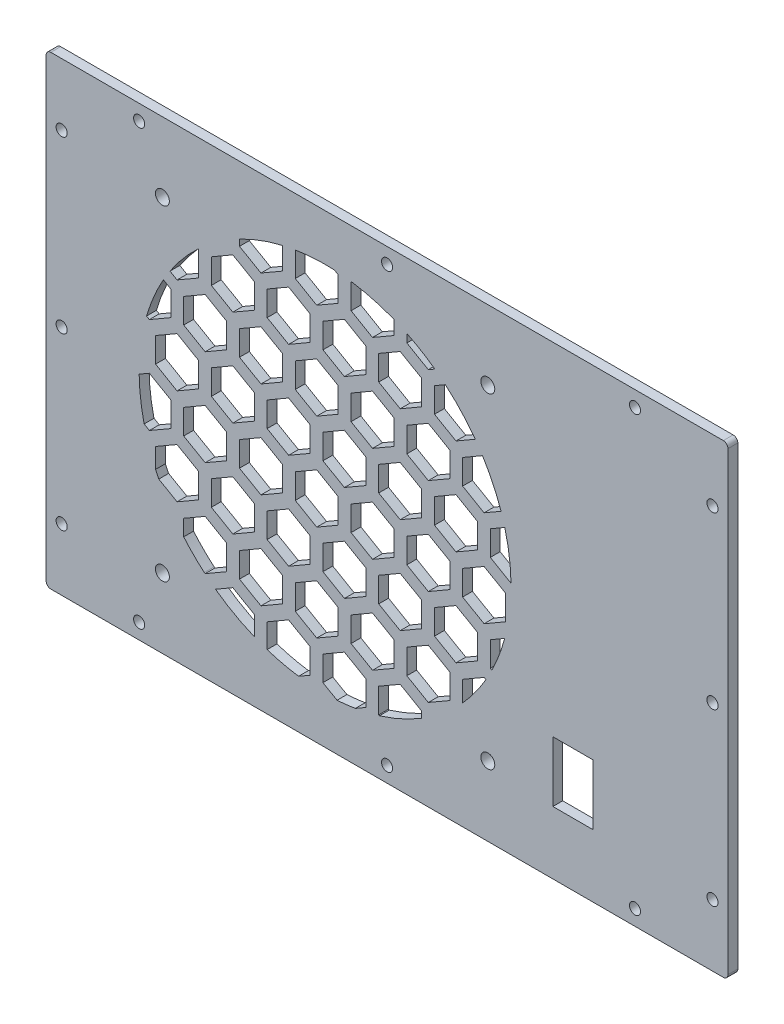
SolidWorks part; units mm, degrees
ref_plane "Front Plane" through (0, 0, 0) normal (0, 0, 1) x (1, 0, 0)
ref_plane "Top Plane" through (0, 0, 0) normal (0, 1, 0) x (1, 0, 0)
ref_plane "Right Plane" through (0, 0, 0) normal (1, 0, 0) x (0, 0, -1)
sketch "Sketch1" plane through (0, 0, 0) normal (0, 0, 1) x (1, 0, 0)
  line L0 (0, 0) -> (0, 75) construction
  line L1 (-110, -75) -> (110, -75)
  line L2 (-110, -75) -> (-110, 75)
  line L3 (-110, 75) -> (110, 75)
  line L4 (110, -75) -> (110, 75)
  line L5 (-110, -75) -> (110, 75) construction
  line L6 (-110, 75) -> (110, -75) construction
  line L15 (0, 0) -> (-110, 0) construction
  point P0 (0, 0)
  dimension "D1" = 220
  dimension "D2" = 150
extrude "Boss-Extrude1" add sketch "Sketch1" along normal blind 3.175 contours L3 L2 L1 L4 region at (0, 0, 0)
hole_wizard "M3 Clearance Hole1" positions "Sketch2" profile "Sketch3" hole size "M3" standard "ANSI Metric" end condition through all
sketch "Sketch2" plane through (0, 0, 3.175) normal (0, 0, 1) x (1, 0, 0)
  line L1 (-105, -70) -> (105, -70)
  line L2 (-105, -70) -> (-105, 70)
  line L3 (-105, 70) -> (105, 70)
  line L4 (105, -70) -> (105, 70)
  line L5 (-105, -70) -> (105, 70) construction
  line L6 (-105, 70) -> (105, -70) construction
  line L7 (-110, -75) -> (-110, 75) construction
  line L8 (-110, 75) -> (110, 75) construction
  point P2 (0, 0)
  point P113 (-80, 70)
  point P115 (80, 70)
  point P116 (0, 70)
  point P118 (-105, 55)
  point P120 (-105, 0)
  point P122 (-105, -55)
  point P124 (-80, -70)
  point P126 (0, -70)
  point P128 (80, -70)
  point P130 (105, -55)
  point P132 (105, 0)
  point P134 (105, 55)
  dimension "D1" = 5
  dimension "D2" = 5
  dimension "D3" = 80
  dimension "D4" = 80
  dimension "D5" = 55
  dimension "D6" = 55
sketch "Sketch3" plane through (0, 0, 3.175) normal (1, 0, 0) x (0, -1, 0)
  line L0 (0, 0) -> (0, 3.175)
  line L1 (0, 3.175) -> (1.8, 3.175)
  line L2 (1.8, 3.175) -> (1.8, 0)
  line L5 (1.8, 0) -> (0, 0)
  line L11 (0, -6.35) -> (0, 107.95) construction
  dimension "Thru Hole Dia." = 3.6
  dimension "Thru Hole Depth" = 3.175
sketch "Sketch4" plane through (0, 0, 3.175) normal (0, 0, 1) x (1, 0, 0)
  line L1 (-5, -5) -> (5, -5)
  line L2 (-5, -5) -> (-5, 5)
  line L3 (-5, 5) -> (5, 5)
  line L4 (5, -5) -> (5, 5)
  line L5 (-5, -5) -> (5, 5) construction
  line L6 (-5, 5) -> (5, -5) construction
  point P0 (0, 0)
  dimension "D1" = 10
  dimension "D2" = 10
extrude "Boss-Extrude2" add sketch "Sketch4" against normal through all
fillet "Fillet2" radius 1.5 4 edges at (-110, -75, 1.5875) (110, -75, 1.5875) (110, 75, 1.5875) (-110, 75, 1.5875)
sketch "Sketch6" plane through (0, 0, 3.175) normal (0, 0, 1) x (1, 0, 0)
  line L0 (-108.5, -75) -> (108.5, -75) construction
  line L1 (-80, -60) -> (40, -60)
  line L2 (-80, -60) -> (-80, 60)
  line L3 (-80, 60) -> (40, 60)
  line L4 (40, -60) -> (40, 60)
  line L5 (-80, -60) -> (40, 60) construction
  line L6 (-80, 60) -> (40, -60) construction
  line L13 (-110, -73.5) -> (-110, 73.5) construction
  line L17 (-72.5, -52.5) -> (32.5, -52.5)
  line L18 (-72.5, -52.5) -> (-72.5, 52.5)
  line L19 (-72.5, 52.5) -> (32.5, 52.5)
  line L20 (32.5, -52.5) -> (32.5, 52.5)
  line L21 (-72.5, -52.5) -> (32.5, 52.5) construction
  line L22 (-72.5, 52.5) -> (32.5, -52.5) construction
  circle A0 centre (-20, 0) radius 60
  point P0 (-20, 0)
  point P5 (-20, 0)
  point P6 (-20, 0)
  dimension "D7" = 120
  dimension "D1" = 120
  dimension "D2" = 120
  dimension "D3" = 15
  dimension "D4" = 30
  dimension "D5" = 105
  dimension "D6" = 105
hole_wizard "M4 Clearance Hole1" positions "Sketch7" profile "Sketch9" hole size "M4" standard "ANSI Metric" end condition through all
sketch "Sketch7" plane through (0, 0, 3.175) normal (0, 0, 1) x (1, 0, 0)
  point P0 (-72.5, 52.5)
  point P3 (32.5, 52.5)
  point P6 (32.5, -52.5)
  point P9 (-72.5, -52.5)
sketch "Sketch9" plane through (-72.5, 52.5, 3.175) normal (1, 0, 0) x (0, -1, 0)
  line L0 (0, 0) -> (0, 3.175)
  line L1 (0, 3.175) -> (2.25, 3.175)
  line L2 (2.25, 3.175) -> (2.25, 0)
  line L5 (2.25, 0) -> (0, 0)
  line L11 (0, -6.35) -> (0, 107.95) construction
  dimension "Thru Hole Dia." = 4.5
  dimension "Thru Hole Depth" = 3.175
extrude "Cut-Extrude1" cut sketch "Sketch6" against normal blind 10 contours L20 A0 L19 L18 L17 | L18 A0 | L19 A0 | A0 L20 | L17 A0 region at (-20, -55.5167, 3.175) region at (-75.5167, 0, 3.175) region at (-20, 0, 3.175) region at (35.5167, 0, 3.175) region at (-20, 55.5167, 3.175)
sketch "Sketch11" plane through (0, 0, 3.175) normal (0, 0, 1) x (1, 0, 0)
  line L0 (-58.6995, -29.7786) -> (-65.6277, -33.7786)
  line L1 (-76.6995, -29.7786) -> (-83.6277, -33.7786)
  line L2 (-83.6277, -33.7786) -> (-83.6277, -41.7786)
  line L3 (-83.6277, -41.7786) -> (-76.6995, -45.7786)
  line L4 (-76.6995, -45.7786) -> (-69.7713, -41.7786)
  line L5 (-69.7713, -41.7786) -> (-69.7713, -33.7786)
  line L6 (-69.7713, -33.7786) -> (-76.6995, -29.7786)
  line L13 (-67.7713, -45.2427) -> (-74.6995, -49.2427)
  line L14 (-74.6995, -49.2427) -> (-74.6995, -57.2427)
  line L15 (-74.6995, -57.2427) -> (-67.7713, -61.2427)
  line L16 (-67.7713, -61.2427) -> (-60.8431, -57.2427)
  line L17 (-60.8431, -57.2427) -> (-60.8431, -49.2427)
  line L18 (-60.8431, -49.2427) -> (-67.7713, -45.2427)
  line L19 (-65.6277, -33.7786) -> (-65.6277, -41.7786)
  line L20 (-65.6277, -41.7786) -> (-58.6995, -45.7786)
  line L21 (-58.6995, -45.7786) -> (-51.7713, -41.7786)
  line L22 (-51.7713, -41.7786) -> (-51.7713, -33.7786)
  line L23 (-51.7713, -33.7786) -> (-58.6995, -29.7786)
  line L24 (-49.7713, -45.2427) -> (-56.6995, -49.2427)
  line L25 (-56.6995, -49.2427) -> (-56.6995, -57.2427)
  line L26 (-56.6995, -57.2427) -> (-49.7713, -61.2427)
  line L27 (-49.7713, -61.2427) -> (-42.8431, -57.2427)
  line L28 (-42.8431, -57.2427) -> (-42.8431, -49.2427)
  line L29 (-42.8431, -49.2427) -> (-49.7713, -45.2427)
  line L30 (-40.6995, -29.7786) -> (-47.6277, -33.7786)
  line L31 (-47.6277, -33.7786) -> (-47.6277, -41.7786)
  line L32 (-47.6277, -41.7786) -> (-40.6995, -45.7786)
  line L33 (-40.6995, -45.7786) -> (-33.7713, -41.7786)
  line L34 (-33.7713, -41.7786) -> (-33.7713, -33.7786)
  line L35 (-33.7713, -33.7786) -> (-40.6995, -29.7786)
  line L36 (-31.7713, -45.2427) -> (-38.6995, -49.2427)
  line L37 (-38.6995, -49.2427) -> (-38.6995, -57.2427)
  line L38 (-38.6995, -57.2427) -> (-31.7713, -61.2427)
  line L39 (-31.7713, -61.2427) -> (-24.8431, -57.2427)
  line L40 (-24.8431, -57.2427) -> (-24.8431, -49.2427)
  line L41 (-24.8431, -49.2427) -> (-31.7713, -45.2427)
  line L42 (-22.6995, -29.7786) -> (-29.6277, -33.7786)
  line L43 (-29.6277, -33.7786) -> (-29.6277, -41.7786)
  line L44 (-29.6277, -41.7786) -> (-22.6995, -45.7786)
  line L45 (-22.6995, -45.7786) -> (-15.7713, -41.7786)
  line L46 (-15.7713, -41.7786) -> (-15.7713, -33.7786)
  line L47 (-15.7713, -33.7786) -> (-22.6995, -29.7786)
  line L48 (-13.7713, -45.2427) -> (-20.6995, -49.2427)
  line L49 (-20.6995, -49.2427) -> (-20.6995, -57.2427)
  line L50 (-20.6995, -57.2427) -> (-13.7713, -61.2427)
  line L51 (-13.7713, -61.2427) -> (-6.8431, -57.2427)
  line L52 (-6.8431, -57.2427) -> (-6.8431, -49.2427)
  line L53 (-6.8431, -49.2427) -> (-13.7713, -45.2427)
  line L54 (-4.6995, -29.7786) -> (-11.6277, -33.7786)
  line L55 (-11.6277, -33.7786) -> (-11.6277, -41.7786)
  line L56 (-11.6277, -41.7786) -> (-4.6995, -45.7786)
  line L57 (-4.6995, -45.7786) -> (2.2287, -41.7786)
  line L58 (2.2287, -41.7786) -> (2.2287, -33.7786)
  line L59 (2.2287, -33.7786) -> (-4.6995, -29.7786)
  line L60 (4.2287, -45.2427) -> (-2.6995, -49.2427)
  line L61 (-2.6995, -49.2427) -> (-2.6995, -57.2427)
  line L62 (-2.6995, -57.2427) -> (4.2287, -61.2427)
  line L63 (4.2287, -61.2427) -> (11.1569, -57.2427)
  line L64 (11.1569, -57.2427) -> (11.1569, -49.2427)
  line L65 (11.1569, -49.2427) -> (4.2287, -45.2427)
  line L66 (13.3005, -29.7786) -> (6.3723, -33.7786)
  line L67 (6.3723, -33.7786) -> (6.3723, -41.7786)
  line L68 (6.3723, -41.7786) -> (13.3005, -45.7786)
  line L69 (13.3005, -45.7786) -> (20.2287, -41.7786)
  line L70 (20.2287, -41.7786) -> (20.2287, -33.7786)
  line L71 (20.2287, -33.7786) -> (13.3005, -29.7786)
  line L72 (22.2287, -45.2427) -> (15.3005, -49.2427)
  line L73 (15.3005, -49.2427) -> (15.3005, -57.2427)
  line L74 (15.3005, -57.2427) -> (22.2287, -61.2427)
  line L75 (22.2287, -61.2427) -> (29.1569, -57.2427)
  line L76 (29.1569, -57.2427) -> (29.1569, -49.2427)
  line L77 (29.1569, -49.2427) -> (22.2287, -45.2427)
  line L78 (31.3005, -29.7786) -> (24.3723, -33.7786)
  line L79 (24.3723, -33.7786) -> (24.3723, -41.7786)
  line L80 (24.3723, -41.7786) -> (31.3005, -45.7786)
  line L81 (31.3005, -45.7786) -> (38.2287, -41.7786)
  line L82 (38.2287, -41.7786) -> (38.2287, -33.7786)
  line L83 (38.2287, -33.7786) -> (31.3005, -29.7786)
  line L84 (40.2287, -45.2427) -> (33.3005, -49.2427)
  line L85 (33.3005, -49.2427) -> (33.3005, -57.2427)
  line L86 (33.3005, -57.2427) -> (40.2287, -61.2427)
  line L87 (40.2287, -61.2427) -> (47.1569, -57.2427)
  line L88 (47.1569, -57.2427) -> (47.1569, -49.2427)
  line L89 (47.1569, -49.2427) -> (40.2287, -45.2427)
  line L90 (-58.6995, 1.2214) -> (-65.6277, -2.7786)
  line L91 (-65.6277, -2.7786) -> (-65.6277, -10.7786)
  line L92 (-65.6277, -10.7786) -> (-58.6995, -14.7786)
  line L93 (-58.6995, -14.7786) -> (-51.7713, -10.7786)
  line L94 (-51.7713, -10.7786) -> (-51.7713, -2.7786)
  line L95 (-51.7713, -2.7786) -> (-58.6995, 1.2214)
  line L96 (-49.7713, -14.2427) -> (-56.6995, -18.2427)
  line L97 (-56.6995, -18.2427) -> (-56.6995, -26.2427)
  line L98 (-56.6995, -26.2427) -> (-49.7713, -30.2427)
  line L99 (-49.7713, -30.2427) -> (-42.8431, -26.2427)
  line L100 (-42.8431, -26.2427) -> (-42.8431, -18.2427)
  line L101 (-42.8431, -18.2427) -> (-49.7713, -14.2427)
  line L102 (-40.6995, 1.2214) -> (-47.6277, -2.7786)
  line L103 (-47.6277, -2.7786) -> (-47.6277, -10.7786)
  line L104 (-47.6277, -10.7786) -> (-40.6995, -14.7786)
  line L105 (-40.6995, -14.7786) -> (-33.7713, -10.7786)
  line L106 (-33.7713, -10.7786) -> (-33.7713, -2.7786)
  line L107 (-33.7713, -2.7786) -> (-40.6995, 1.2214)
  line L108 (-31.7713, -14.2427) -> (-38.6995, -18.2427)
  line L109 (-38.6995, -18.2427) -> (-38.6995, -26.2427)
  line L110 (-38.6995, -26.2427) -> (-31.7713, -30.2427)
  line L111 (-31.7713, -30.2427) -> (-24.8431, -26.2427)
  line L112 (-24.8431, -26.2427) -> (-24.8431, -18.2427)
  line L113 (-24.8431, -18.2427) -> (-31.7713, -14.2427)
  line L114 (-22.6995, 1.2214) -> (-29.6277, -2.7786)
  line L115 (-29.6277, -2.7786) -> (-29.6277, -10.7786)
  line L116 (-29.6277, -10.7786) -> (-22.6995, -14.7786)
  line L117 (-22.6995, -14.7786) -> (-15.7713, -10.7786)
  line L118 (-15.7713, -10.7786) -> (-15.7713, -2.7786)
  line L119 (-15.7713, -2.7786) -> (-22.6995, 1.2214)
  line L120 (-13.7713, -14.2427) -> (-20.6995, -18.2427)
  line L121 (-20.6995, -18.2427) -> (-20.6995, -26.2427)
  line L122 (-20.6995, -26.2427) -> (-13.7713, -30.2427)
  line L123 (-13.7713, -30.2427) -> (-6.8431, -26.2427)
  line L124 (-6.8431, -26.2427) -> (-6.8431, -18.2427)
  line L125 (-6.8431, -18.2427) -> (-13.7713, -14.2427)
  line L126 (-4.6995, 1.2214) -> (-11.6277, -2.7786)
  line L127 (-11.6277, -2.7786) -> (-11.6277, -10.7786)
  line L128 (-11.6277, -10.7786) -> (-4.6995, -14.7786)
  line L129 (-4.6995, -14.7786) -> (2.2287, -10.7786)
  line L130 (2.2287, -10.7786) -> (2.2287, -2.7786)
  line L131 (2.2287, -2.7786) -> (-4.6995, 1.2214)
  line L132 (4.2287, -14.2427) -> (-2.6995, -18.2427)
  line L133 (-2.6995, -18.2427) -> (-2.6995, -26.2427)
  line L134 (-2.6995, -26.2427) -> (4.2287, -30.2427)
  line L135 (4.2287, -30.2427) -> (11.1569, -26.2427)
  line L136 (11.1569, -26.2427) -> (11.1569, -18.2427)
  line L137 (11.1569, -18.2427) -> (4.2287, -14.2427)
  line L138 (13.3005, 1.2214) -> (6.3723, -2.7786)
  line L139 (6.3723, -2.7786) -> (6.3723, -10.7786)
  line L140 (6.3723, -10.7786) -> (13.3005, -14.7786)
  line L141 (13.3005, -14.7786) -> (20.2287, -10.7786)
  line L142 (20.2287, -10.7786) -> (20.2287, -2.7786)
  line L143 (20.2287, -2.7786) -> (13.3005, 1.2214)
  line L144 (22.2287, -14.2427) -> (15.3005, -18.2427)
  line L145 (15.3005, -18.2427) -> (15.3005, -26.2427)
  line L146 (15.3005, -26.2427) -> (22.2287, -30.2427)
  line L147 (22.2287, -30.2427) -> (29.1569, -26.2427)
  line L148 (29.1569, -26.2427) -> (29.1569, -18.2427)
  line L149 (29.1569, -18.2427) -> (22.2287, -14.2427)
  line L150 (31.3005, 1.2214) -> (24.3723, -2.7786)
  line L151 (24.3723, -2.7786) -> (24.3723, -10.7786)
  line L152 (24.3723, -10.7786) -> (31.3005, -14.7786)
  line L153 (31.3005, -14.7786) -> (38.2287, -10.7786)
  line L154 (38.2287, -10.7786) -> (38.2287, -2.7786)
  line L155 (38.2287, -2.7786) -> (31.3005, 1.2214)
  line L156 (40.2287, -14.2427) -> (33.3005, -18.2427)
  line L157 (33.3005, -18.2427) -> (33.3005, -26.2427)
  line L158 (33.3005, -26.2427) -> (40.2287, -30.2427)
  line L159 (40.2287, -30.2427) -> (47.1569, -26.2427)
  line L160 (47.1569, -26.2427) -> (47.1569, -18.2427)
  line L161 (47.1569, -18.2427) -> (40.2287, -14.2427)
  line L162 (-58.6995, 32.2214) -> (-65.6277, 28.2214)
  line L163 (-65.6277, 28.2214) -> (-65.6277, 20.2214)
  line L164 (-65.6277, 20.2214) -> (-58.6995, 16.2214)
  line L165 (-58.6995, 16.2214) -> (-51.7713, 20.2214)
  line L166 (-51.7713, 20.2214) -> (-51.7713, 28.2214)
  line L167 (-51.7713, 28.2214) -> (-58.6995, 32.2214)
  line L168 (-49.7713, 16.7573) -> (-56.6995, 12.7573)
  line L169 (-56.6995, 12.7573) -> (-56.6995, 4.7573)
  line L170 (-56.6995, 4.7573) -> (-49.7713, 0.7573)
  line L171 (-49.7713, 0.7573) -> (-42.8431, 4.7573)
  line L172 (-42.8431, 4.7573) -> (-42.8431, 12.7573)
  line L173 (-42.8431, 12.7573) -> (-49.7713, 16.7573)
  line L174 (-40.6995, 32.2214) -> (-47.6277, 28.2214)
  line L175 (-47.6277, 28.2214) -> (-47.6277, 20.2214)
  line L176 (-47.6277, 20.2214) -> (-40.6995, 16.2214)
  line L177 (-40.6995, 16.2214) -> (-33.7713, 20.2214)
  line L178 (-33.7713, 20.2214) -> (-33.7713, 28.2214)
  line L179 (-33.7713, 28.2214) -> (-40.6995, 32.2214)
  line L180 (-31.7713, 16.7573) -> (-38.6995, 12.7573)
  line L181 (-38.6995, 12.7573) -> (-38.6995, 4.7573)
  line L182 (-38.6995, 4.7573) -> (-31.7713, 0.7573)
  line L183 (-31.7713, 0.7573) -> (-24.8431, 4.7573)
  line L184 (-24.8431, 4.7573) -> (-24.8431, 12.7573)
  line L185 (-24.8431, 12.7573) -> (-31.7713, 16.7573)
  line L186 (-22.6995, 32.2214) -> (-29.6277, 28.2214)
  line L187 (-29.6277, 28.2214) -> (-29.6277, 20.2214)
  line L188 (-29.6277, 20.2214) -> (-22.6995, 16.2214)
  line L189 (-22.6995, 16.2214) -> (-15.7713, 20.2214)
  line L190 (-15.7713, 20.2214) -> (-15.7713, 28.2214)
  line L191 (-15.7713, 28.2214) -> (-22.6995, 32.2214)
  line L192 (-13.7713, 16.7573) -> (-20.6995, 12.7573)
  line L193 (-20.6995, 12.7573) -> (-20.6995, 4.7573)
  line L194 (-20.6995, 4.7573) -> (-13.7713, 0.7573)
  line L195 (-13.7713, 0.7573) -> (-6.8431, 4.7573)
  line L196 (-6.8431, 4.7573) -> (-6.8431, 12.7573)
  line L197 (-6.8431, 12.7573) -> (-13.7713, 16.7573)
  line L198 (-4.6995, 32.2214) -> (-11.6277, 28.2214)
  line L199 (-11.6277, 28.2214) -> (-11.6277, 20.2214)
  line L200 (-11.6277, 20.2214) -> (-4.6995, 16.2214)
  line L201 (-4.6995, 16.2214) -> (2.2287, 20.2214)
  line L202 (2.2287, 20.2214) -> (2.2287, 28.2214)
  line L203 (2.2287, 28.2214) -> (-4.6995, 32.2214)
  line L204 (4.2287, 16.7573) -> (-2.6995, 12.7573)
  line L205 (-2.6995, 12.7573) -> (-2.6995, 4.7573)
  line L206 (-2.6995, 4.7573) -> (4.2287, 0.7573)
  line L207 (4.2287, 0.7573) -> (11.1569, 4.7573)
  line L208 (11.1569, 4.7573) -> (11.1569, 12.7573)
  line L209 (11.1569, 12.7573) -> (4.2287, 16.7573)
  line L210 (13.3005, 32.2214) -> (6.3723, 28.2214)
  line L211 (6.3723, 28.2214) -> (6.3723, 20.2214)
  line L212 (6.3723, 20.2214) -> (13.3005, 16.2214)
  line L213 (13.3005, 16.2214) -> (20.2287, 20.2214)
  line L214 (20.2287, 20.2214) -> (20.2287, 28.2214)
  line L215 (20.2287, 28.2214) -> (13.3005, 32.2214)
  line L216 (22.2287, 16.7573) -> (15.3005, 12.7573)
  line L217 (15.3005, 12.7573) -> (15.3005, 4.7573)
  line L218 (15.3005, 4.7573) -> (22.2287, 0.7573)
  line L219 (22.2287, 0.7573) -> (29.1569, 4.7573)
  line L220 (29.1569, 4.7573) -> (29.1569, 12.7573)
  line L221 (29.1569, 12.7573) -> (22.2287, 16.7573)
  line L222 (31.3005, 32.2214) -> (24.3723, 28.2214)
  line L223 (24.3723, 28.2214) -> (24.3723, 20.2214)
  line L224 (24.3723, 20.2214) -> (31.3005, 16.2214)
  line L225 (31.3005, 16.2214) -> (38.2287, 20.2214)
  line L226 (38.2287, 20.2214) -> (38.2287, 28.2214)
  line L227 (38.2287, 28.2214) -> (31.3005, 32.2214)
  line L228 (40.2287, 16.7573) -> (33.3005, 12.7573)
  line L229 (33.3005, 12.7573) -> (33.3005, 4.7573)
  line L230 (33.3005, 4.7573) -> (40.2287, 0.7573)
  line L231 (40.2287, 0.7573) -> (47.1569, 4.7573)
  line L232 (47.1569, 4.7573) -> (47.1569, 12.7573)
  line L233 (47.1569, 12.7573) -> (40.2287, 16.7573)
  line L234 (-58.6995, 63.2214) -> (-65.6277, 59.2214)
  line L235 (-65.6277, 59.2214) -> (-65.6277, 51.2214)
  line L236 (-65.6277, 51.2214) -> (-58.6995, 47.2214)
  line L237 (-58.6995, 47.2214) -> (-51.7713, 51.2214)
  line L238 (-51.7713, 51.2214) -> (-51.7713, 59.2214)
  line L239 (-51.7713, 59.2214) -> (-58.6995, 63.2214)
  line L240 (-49.7713, 47.7573) -> (-56.6995, 43.7573)
  line L241 (-56.6995, 43.7573) -> (-56.6995, 35.7573)
  line L242 (-56.6995, 35.7573) -> (-49.7713, 31.7573)
  line L243 (-49.7713, 31.7573) -> (-42.8431, 35.7573)
  line L244 (-42.8431, 35.7573) -> (-42.8431, 43.7573)
  line L245 (-42.8431, 43.7573) -> (-49.7713, 47.7573)
  line L246 (-40.6995, 63.2214) -> (-47.6277, 59.2214)
  line L247 (-47.6277, 59.2214) -> (-47.6277, 51.2214)
  line L248 (-47.6277, 51.2214) -> (-40.6995, 47.2214)
  line L249 (-40.6995, 47.2214) -> (-33.7713, 51.2214)
  line L250 (-33.7713, 51.2214) -> (-33.7713, 59.2214)
  line L251 (-33.7713, 59.2214) -> (-40.6995, 63.2214)
  line L252 (-31.7713, 47.7573) -> (-38.6995, 43.7573)
  line L253 (-38.6995, 43.7573) -> (-38.6995, 35.7573)
  line L254 (-38.6995, 35.7573) -> (-31.7713, 31.7573)
  line L255 (-31.7713, 31.7573) -> (-24.8431, 35.7573)
  line L256 (-24.8431, 35.7573) -> (-24.8431, 43.7573)
  line L257 (-24.8431, 43.7573) -> (-31.7713, 47.7573)
  line L258 (-22.6995, 63.2214) -> (-29.6277, 59.2214)
  line L259 (-29.6277, 59.2214) -> (-29.6277, 51.2214)
  line L260 (-29.6277, 51.2214) -> (-22.6995, 47.2214)
  line L261 (-22.6995, 47.2214) -> (-15.7713, 51.2214)
  line L262 (-15.7713, 51.2214) -> (-15.7713, 59.2214)
  line L263 (-15.7713, 59.2214) -> (-22.6995, 63.2214)
  line L264 (-13.7713, 47.7573) -> (-20.6995, 43.7573)
  line L265 (-20.6995, 43.7573) -> (-20.6995, 35.7573)
  line L266 (-20.6995, 35.7573) -> (-13.7713, 31.7573)
  line L267 (-13.7713, 31.7573) -> (-6.8431, 35.7573)
  line L268 (-6.8431, 35.7573) -> (-6.8431, 43.7573)
  line L269 (-6.8431, 43.7573) -> (-13.7713, 47.7573)
  line L270 (-4.6995, 63.2214) -> (-11.6277, 59.2214)
  line L271 (-11.6277, 59.2214) -> (-11.6277, 51.2214)
  line L272 (-11.6277, 51.2214) -> (-4.6995, 47.2214)
  line L273 (-4.6995, 47.2214) -> (2.2287, 51.2214)
  line L274 (2.2287, 51.2214) -> (2.2287, 59.2214)
  line L275 (2.2287, 59.2214) -> (-4.6995, 63.2214)
  line L276 (4.2287, 47.7573) -> (-2.6995, 43.7573)
  line L277 (-2.6995, 43.7573) -> (-2.6995, 35.7573)
  line L278 (-2.6995, 35.7573) -> (4.2287, 31.7573)
  line L279 (4.2287, 31.7573) -> (11.1569, 35.7573)
  line L280 (11.1569, 35.7573) -> (11.1569, 43.7573)
  line L281 (11.1569, 43.7573) -> (4.2287, 47.7573)
  line L282 (13.3005, 63.2214) -> (6.3723, 59.2214)
  line L283 (6.3723, 59.2214) -> (6.3723, 51.2214)
  line L284 (6.3723, 51.2214) -> (13.3005, 47.2214)
  line L285 (13.3005, 47.2214) -> (20.2287, 51.2214)
  line L286 (20.2287, 51.2214) -> (20.2287, 59.2214)
  line L287 (20.2287, 59.2214) -> (13.3005, 63.2214)
  line L288 (22.2287, 47.7573) -> (15.3005, 43.7573)
  line L289 (15.3005, 43.7573) -> (15.3005, 35.7573)
  line L290 (15.3005, 35.7573) -> (22.2287, 31.7573)
  line L291 (22.2287, 31.7573) -> (29.1569, 35.7573)
  line L292 (29.1569, 35.7573) -> (29.1569, 43.7573)
  line L293 (29.1569, 43.7573) -> (22.2287, 47.7573)
  line L294 (31.3005, 63.2214) -> (24.3723, 59.2214)
  line L295 (24.3723, 59.2214) -> (24.3723, 51.2214)
  line L296 (24.3723, 51.2214) -> (31.3005, 47.2214)
  line L297 (31.3005, 47.2214) -> (38.2287, 51.2214)
  line L298 (38.2287, 51.2214) -> (38.2287, 59.2214)
  line L299 (38.2287, 59.2214) -> (31.3005, 63.2214)
  line L300 (40.2287, 47.7573) -> (33.3005, 43.7573)
  line L301 (33.3005, 43.7573) -> (33.3005, 35.7573)
  line L302 (33.3005, 35.7573) -> (40.2287, 31.7573)
  line L303 (40.2287, 31.7573) -> (47.1569, 35.7573)
  line L304 (47.1569, 35.7573) -> (47.1569, 43.7573)
  line L305 (47.1569, 43.7573) -> (40.2287, 47.7573)
  line L306 (-76.6995, 1.2214) -> (-83.6277, -2.7786)
  line L307 (-83.6277, -2.7786) -> (-83.6277, -10.7786)
  line L308 (-83.6277, -10.7786) -> (-76.6995, -14.7786)
  line L309 (-76.6995, -14.7786) -> (-69.7713, -10.7786)
  line L310 (-69.7713, -10.7786) -> (-69.7713, -2.7786)
  line L311 (-69.7713, -2.7786) -> (-76.6995, 1.2214)
  line L312 (-67.7713, -14.2427) -> (-74.6995, -18.2427)
  line L313 (-74.6995, -18.2427) -> (-74.6995, -26.2427)
  line L314 (-74.6995, -26.2427) -> (-67.7713, -30.2427)
  line L315 (-67.7713, -30.2427) -> (-60.8431, -26.2427)
  line L316 (-60.8431, -26.2427) -> (-60.8431, -18.2427)
  line L317 (-60.8431, -18.2427) -> (-67.7713, -14.2427)
  line L318 (-76.6995, 32.2214) -> (-83.6277, 28.2214)
  line L319 (-83.6277, 28.2214) -> (-83.6277, 20.2214)
  line L320 (-83.6277, 20.2214) -> (-76.6995, 16.2214)
  line L321 (-76.6995, 16.2214) -> (-69.7713, 20.2214)
  line L322 (-69.7713, 20.2214) -> (-69.7713, 28.2214)
  line L323 (-69.7713, 28.2214) -> (-76.6995, 32.2214)
  line L324 (-67.7713, 16.7573) -> (-74.6995, 12.7573)
  line L325 (-74.6995, 12.7573) -> (-74.6995, 4.7573)
  line L326 (-74.6995, 4.7573) -> (-67.7713, 0.7573)
  line L327 (-67.7713, 0.7573) -> (-60.8431, 4.7573)
  line L328 (-60.8431, 4.7573) -> (-60.8431, 12.7573)
  line L329 (-60.8431, 12.7573) -> (-67.7713, 16.7573)
  line L330 (-76.6995, 63.2214) -> (-83.6277, 59.2214)
  line L331 (-83.6277, 59.2214) -> (-83.6277, 51.2214)
  line L332 (-83.6277, 51.2214) -> (-76.6995, 47.2214)
  line L333 (-76.6995, 47.2214) -> (-69.7713, 51.2214)
  line L334 (-69.7713, 51.2214) -> (-69.7713, 59.2214)
  line L335 (-69.7713, 59.2214) -> (-76.6995, 63.2214)
  line L336 (-67.7713, 47.7573) -> (-74.6995, 43.7573)
  line L337 (-74.6995, 43.7573) -> (-74.6995, 35.7573)
  line L338 (-74.6995, 35.7573) -> (-67.7713, 31.7573)
  line L339 (-67.7713, 31.7573) -> (-60.8431, 35.7573)
  line L340 (-60.8431, 35.7573) -> (-60.8431, 43.7573)
  line L341 (-60.8431, 43.7573) -> (-67.7713, 47.7573)
  line L346 (-110, 73.5) -> (-110, -73.5)
  line L347 (-108.5, -75) -> (108.5, -75)
  line L348 (110, -73.5) -> (110, 73.5)
  line L349 (108.5, 75) -> (-108.5, 75)
  line L350 (-110, 73.5) -> (-110, -73.5)
  line L351 (-108.5, -75) -> (108.5, -75)
  line L352 (110, -73.5) -> (110, 73.5)
  line L353 (108.5, 75) -> (-108.5, 75)
  circle A0 centre (-76.6995, -37.7786) radius 6.9282 construction
  circle A2 centre (-67.7713, -53.2427) radius 6.9282 construction
  arc A7 (-110, -73.5) -> (-108.5, -75) centre (-108.5, -73.5) ccw
  arc A8 (108.5, -75) -> (110, -73.5) centre (108.5, -73.5) ccw
  arc A9 (110, 73.5) -> (108.5, 75) centre (108.5, 73.5) ccw
  arc A10 (-108.5, 75) -> (-110, 73.5) centre (-108.5, 73.5) ccw
  arc A11 (-110, -73.5) -> (-108.5, -75) centre (-108.5, -73.5) ccw
  arc A12 (108.5, -75) -> (110, -73.5) centre (108.5, -73.5) ccw
  arc A13 (110, 73.5) -> (108.5, 75) centre (108.5, 73.5) ccw
  arc A14 (-108.5, 75) -> (-110, 73.5) centre (-108.5, 73.5) ccw
  circle M347 centre (-20, 0) radius 60
  dimension "D1" = 8
  dimension "D2" = 4
  dimension "D3" = 2
  dimension "D6" = 0
  dimension "D4" = 7
  dimension "D5" = 4
extrude "Boss-Extrude3" add sketch "Sketch11" against normal up to surface (3.175 mm away) contours L341 L340 L339 L338 L323 L322 L321 L320 L306 L311 L310 L309 L308 L313 L312 L317 L316 L315 L314 L19 L0 L23 L22 L21 L20 L24 L29 L28 L37 L36 L41 L40 L39 L50 L49 L48 L53 L52 L51 L62 L61 L60 L65 M347 region at (-20.0079, 0.1732, 3.175) up to face at (40, 0, 0)
sketch "Sketch12" plane through (0, 0, 3.175) normal (0, 0, 1) x (1, 0, 0)
  line L0 (110, -73.5) -> (110, 73.5) construction
  line L1 (53.5, -54.75) -> (66.5, -54.75)
  line L2 (53.5, -54.75) -> (53.5, -35.25)
  line L3 (53.5, -35.25) -> (66.5, -35.25)
  line L4 (66.5, -54.75) -> (66.5, -35.25)
  line L5 (53.5, -54.75) -> (66.5, -35.25) construction
  line L6 (53.5, -35.25) -> (66.5, -54.75) construction
  line L7 (-108.5, -75) -> (108.5, -75) construction
  point P0 (60, -45)
  point P5 (55.4533, -48.8137)
  point P6 (55.897, -46.7843)
  dimension "D1" = 13
  dimension "D2" = 19.5
  dimension "D3" = 50
  dimension "D4" = 30
extrude "Cut-Extrude2" cut sketch "Sketch12" against normal through all
